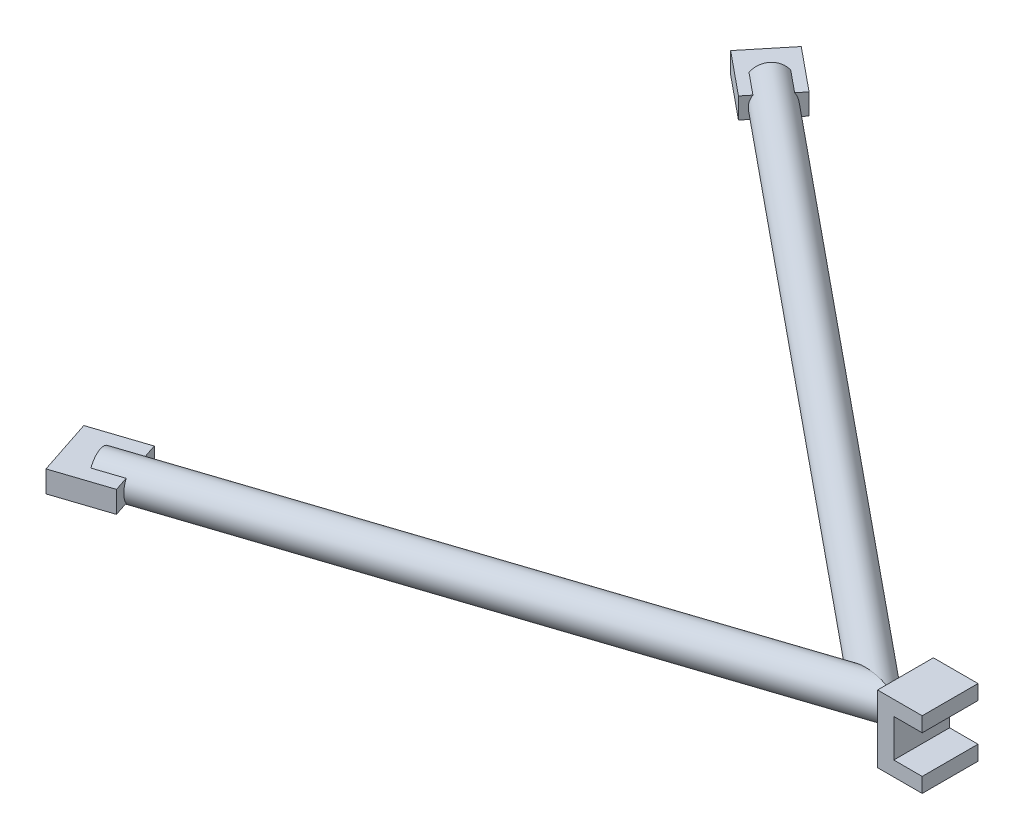
SolidWorks part; units mm, degrees
ref_plane "Front Plane" through (0, 0, 0) normal (0, 0, 1) x (1, 0, 0)
ref_plane "Top Plane" through (0, 0, 0) normal (0, 1, 0) x (1, 0, 0)
ref_plane "Right Plane" through (0, 0, 0) normal (1, 0, 0) x (0, 0, -1)
sketch "Sketch1" plane through (0, 0, 0) normal (0, 1, 0) x (1, 0, 0)
  line L0 (-265.3198, -87.5771) -> (0, 0)
  line L1 (0, 0) -> (-265.3198, 217.2229)
  line L2 (-265.3198, 217.2229) -> (-265.3198, -87.5771) construction
  dimension "D1" = 279.4
  dimension "D2" = 342.9
  dimension "D3" = 304.8
ref_plane "Plane1" through (-265.3198, 0, 87.5771) normal (0.9496, 0, -0.3134) x (-0.3134, 0, -0.9496)
sketch "Sketch2" plane through (-265.3198, 0, 87.5771) normal (0.9496, 0, -0.3134) x (-0.3134, 0, -0.9496)
  circle A0 centre (0, 0) radius 8.255
  dimension "D1" = 16.51
sweep "Sweep1" add profiles "Sketch2" path "Sketch1"
sketch "Sketch3" plane through (0, 0, 0) normal (0, 0, 1) x (1, 0, 0)
  line L0 (33.9318, 15.3155) -> (13.6294, 15.3155)
  line L1 (13.6294, 15.3155) -> (13.6294, -15.3155)
  line L2 (13.6294, -15.3155) -> (33.9318, -15.3155)
  line L3 (33.9318, -15.3155) -> (33.9318, -8.5938)
  line L4 (33.9318, -8.5938) -> (21.0046, -8.5938)
  line L5 (21.0046, -8.5938) -> (21.0046, 8.5938)
  line L6 (21.0046, 8.5938) -> (33.9318, 8.5938)
  line L7 (33.9318, 8.5938) -> (33.9318, 15.3155)
  line L8 (16.854, 0) -> (-16.854, 0) construction
  ellipse E0 centre (0, 0) end of major axis (16.854, 0) minor radius 8.255 construction
  ellipse E1 centre (0, 0) end of major axis (16.854, 0) minor radius 8.255 construction
  point P21 (13.6294, 0)
extrude "Boss-Extrude1" add sketch "Sketch3" along normal blind 12.7 and the other way blind 12.7
sketch "Sketch4" plane through (-265.3198, 0, 87.5771) normal (-0.9496, 0, 0.3134) x (0.3134, 0, 0.9496)
  line L1 (-13.522, 4.9357) -> (13.522, 4.9357)
  line L2 (-13.522, 4.9357) -> (-13.522, -4.9357)
  line L3 (-13.522, -4.9357) -> (13.522, -4.9357)
  line L4 (13.522, 4.9357) -> (13.522, -4.9357)
  line L5 (-13.522, 4.9357) -> (13.522, -4.9357) construction
  line L6 (-13.522, -4.9357) -> (13.522, 4.9357) construction
  circle A1 centre (0, 0) radius 8.255
  circle A2 centre (0, 0) radius 8.255 construction
  dimension "D1" = 0
extrude "Boss-Extrude2" add sketch "Sketch4" along normal blind 12.7 and the other way blind 12.7
sketch "Sketch5" plane through (-265.3198, 0, -217.2229) normal (-0.7738, 0, -0.6335) x (-0.6335, 0, 0.7738)
  line L1 (-11.4198, 4.7605) -> (11.4198, 4.7605)
  line L2 (-11.4198, 4.7605) -> (-11.4198, -4.7605)
  line L3 (-11.4198, -4.7605) -> (11.4198, -4.7605)
  line L4 (11.4198, 4.7605) -> (11.4198, -4.7605)
  line L5 (-11.4198, 4.7605) -> (11.4198, -4.7605) construction
  line L6 (-11.4198, -4.7605) -> (11.4198, 4.7605) construction
  point P0 (0, 0)
extrude "Boss-Extrude3" add sketch "Sketch5" along normal blind 12.7 and the other way blind 12.7
